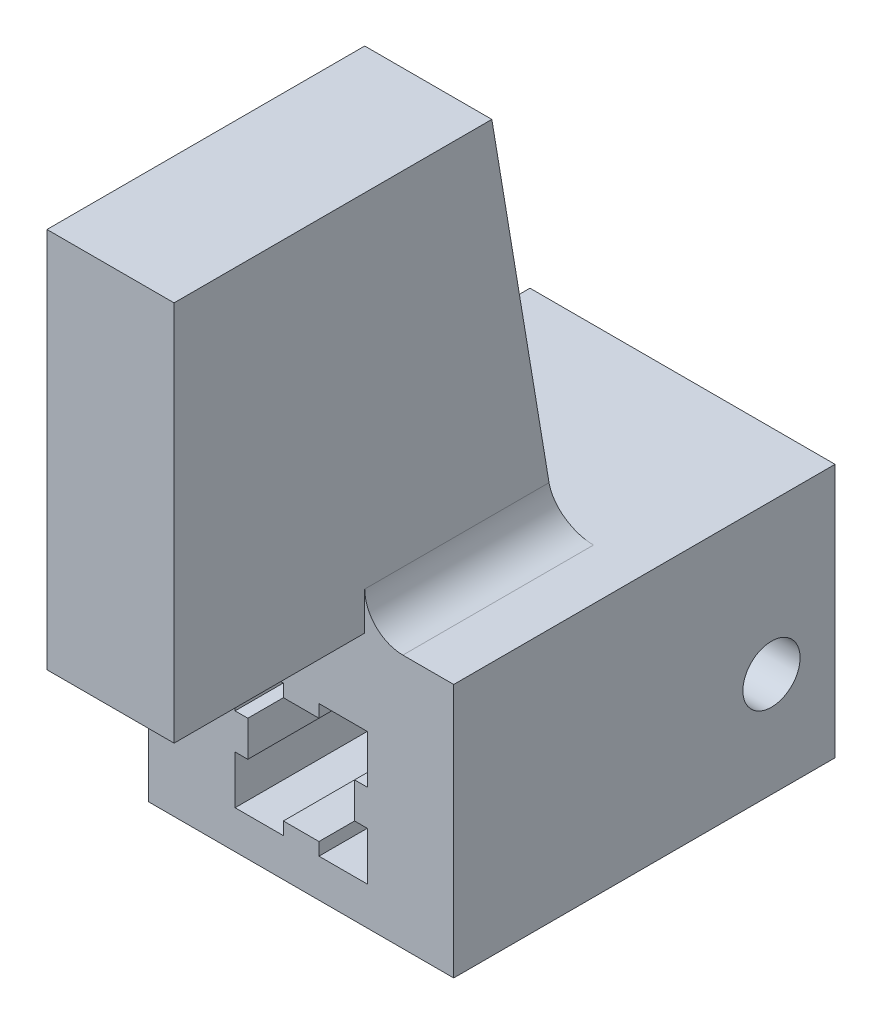
SolidWorks part; units mm, degrees
ref_plane "Front Plane" through (0, 0, 0) normal (0, 0, 1) x (1, 0, 0)
ref_plane "Top Plane" through (0, 0, 0) normal (0, 1, 0) x (1, 0, 0)
ref_plane "Right Plane" through (0, 0, 0) normal (1, 0, 0) x (0, 0, -1)
sketch "Esquisse1" plane through (0, 0, 0) normal (0, 0, 1) x (1, 0, 0)
  line L1 (-12, 10) -> (12, 10)
  line L2 (-12, 10) -> (-12, -10)
  line L3 (-12, -10) -> (12, -10)
  line L4 (12, 10) -> (12, -10)
  point P4 (0, -10)
  point P5 (-12, 0)
  dimension "D1" = 24
  dimension "D2" = 20
extrude "Main Extrusion" add sketch "Esquisse1" along normal blind 30
sketch "Esquisse3" plane through (0, 0, 0) normal (0, 0, -1) x (-1, 0, 0)
  line L0 (-5.2, 3.4) -> (-5.2, -0.4)
  line L1 (-5.2, -0.4) -> (-4.2, -0.4)
  line L2 (-4.2, -0.4) -> (-4.2, -3.2)
  line L3 (-4.2, -3.2) -> (-5.2, -3.2)
  line L4 (-5.2, -3.2) -> (-5.2, -7)
  line L5 (-5.2, -7) -> (-1.4, -7)
  line L6 (-1.4, -7) -> (-1.4, -6)
  line L7 (-1.4, -6) -> (1.4, -6)
  line L8 (1.4, -6) -> (1.4, -7)
  line L9 (1.4, -7) -> (5.2, -7)
  line L10 (5.2, -7) -> (5.2, -3.2)
  line L11 (5.2, -3.2) -> (4.2, -3.2)
  line L12 (4.2, -3.2) -> (4.2, -0.4)
  line L13 (4.2, -0.4) -> (5.2, -0.4)
  line L14 (5.2, -0.4) -> (5.2, 3.4)
  line L15 (5.2, 3.4) -> (1.4, 3.4)
  line L16 (1.4, 3.4) -> (1.4, 2.4)
  line L17 (1.4, 2.4) -> (-1.4, 2.4)
  line L18 (-1.4, 2.4) -> (-1.4, 3.4)
  line L19 (-1.4, 3.4) -> (-5.2, 3.4)
  line L21 (12, -10) -> (-12, -10) construction
  point P20 (0, -6)
  point P24 (0, -10)
  dimension "D1" = 2.8
  dimension "D2" = 10.4
  dimension "D3" = 1
  dimension "D4" = 1
  dimension "D5" = 3
extrude "Main Riding Hole" cut sketch "Esquisse3" against normal through all
sketch "Esquisse4" plane through (-12, 0, 0) normal (-1, 0, 0) x (0, 0, 1)
  line L1 (0, -3.2) -> (0, -0.4) construction
  line L2 (0, 10) -> (0, -10) construction
  circle A0 centre (5, -1.8) radius 2.25
  point P5 (0, -1.8)
  dimension "D1" = 4.5
  dimension "D2" = 5
extrude "TractorHole" cut sketch "Esquisse4" against normal blind 8
mirror "TractorHoleSymetry" about plane through (0, 0, 0) normal (1, 0, 0) of "TractorHole"
sketch "Esquisse5" plane through (0, 0, 0) normal (1, 0, 0) x (0, 0, -1)
  line L0 (-45, 10) -> (-45, 40)
  line L1 (-30, 10) -> (0, 10) construction
  line L2 (-45, 40) -> (-20, 40)
  line L3 (-20, 40) -> (-15, 10)
  line L4 (-15, 10) -> (-45, 10)
  line L6 (-30, -10) -> (-30, 10) construction
  dimension "D1" = 30
  dimension "D2" = 25
  dimension "D3" = 30
  dimension "D4" = 15
extrude "ImpactPiece" add sketch "Esquisse5" against normal mid plane 10
fillet "Congé1" radius 3 2 edges at (-5, 10, 22.5) (5, 10, 22.5)
